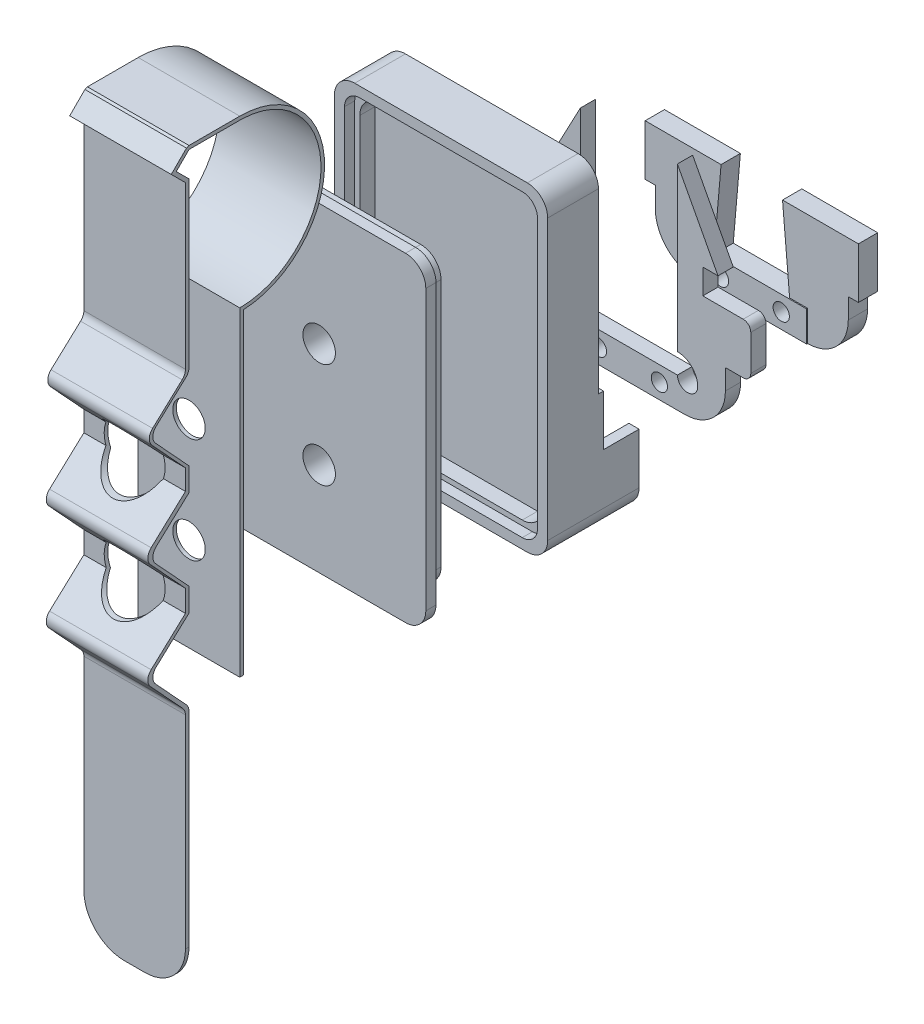
SolidWorks part; units mm, degrees
ref_plane "前视基准面" through (0, 0, 0) normal (0, 0, 1) x (1, 0, 0)
ref_plane "上视基准面" through (0, 0, 0) normal (0, 1, 0) x (1, 0, 0)
ref_plane "右视基准面" through (0, 0, 0) normal (1, 0, 0) x (0, 0, -1)
sketch "草图2" plane through (0, 0, 0) normal (0, 0, 1) x (1, 0, 0)
  line L1 (-21, 31.5) -> (21, 31.5)
  line L2 (-21, 31.5) -> (-21, -31.5)
  line L3 (-21, -31.5) -> (21, -31.5)
  line L4 (21, 31.5) -> (21, -31.5)
  line L5 (-21, 31.5) -> (21, -31.5) construction
  line L6 (-21, -31.5) -> (21, 31.5) construction
  point P0 (0, 0)
extrude "凸台-拉伸1" add sketch "草图2" along normal blind 10
sketch "草图3" plane through (0, 0, 0) normal (0, 0, -1) x (-1, 0, 0)
  line L0 (21, 31.5) -> (21, -31.5) construction
  line L1 (-21, -31.5) -> (21, -31.5)
  line L2 (-21, -31.5) -> (-21, -7.5)
  line L3 (-21, -7.5) -> (21, -7.5)
  line L4 (21, -31.5) -> (21, -7.5)
extrude "凸台-拉伸2" add sketch "草图3" along normal blind 8
sketch "草图4" plane through (0, -7.5, 0) normal (0, 1, 0) x (1, 0, 0)
  line L0 (0, 0) -> (0, 3)
  line L1 (0, 3) -> (5.5, 3)
  line L2 (0, 3) -> (-5.5, 3)
  line L3 (5.5, 3) -> (3.5, 0)
  line L4 (21, 0) -> (-21, 0) construction
  line L5 (-5.5, 3) -> (-3.5, 0)
  line L6 (0, 0) -> (3.5, 0)
  line L7 (0, 0) -> (-3.5, 0)
  line M4 (-21, 0) -> (21, 0)
  dimension "D1" = 3
extrude "凸台-拉伸3" add sketch "草图4" along normal blind 32 contours L2 L5 L0 M4 | L3 L1 L0 M4 region at (-2.287, -7.5, -1.6111) region at (2.287, -7.5, -1.6111)
sketch "草图5" plane through (0, -7.5, 0) normal (0, 1, 0) x (1, 0, 0)
  line L0 (0, 3) -> (0, 5.5)
  line L1 (5.5, 3) -> (-5.5, 3) construction
  line L3 (-5.05, 3) -> (5.05, 3)
  line L4 (-5.05, 3) -> (-5.05, 5.5)
  line L5 (-5.05, 5.5) -> (5.05, 5.5)
  line L6 (5.05, 3) -> (5.05, 5.5)
  line L7 (-5.05, 3) -> (5.05, 5.5) construction
  line L8 (-5.05, 5.5) -> (5.05, 3) construction
  circle A0 centre (1.27, 4.25) radius 0.74
  circle A1 centre (3.81, 4.25) radius 0.74
  circle A2 centre (-1.27, 4.25) radius 0.74
  circle A3 centre (-3.81, 4.25) radius 0.74
  point P5 (0, 4.25)
  dimension "D3" = 1.27
  dimension "D4" = 1.48
  dimension "D1" = 2.5
  dimension "D2" = 10.1
  dimension "D5" = 2
  dimension "D6" = 3
extrude "切除-拉伸1" cut sketch "草图5" against normal through all contours A3 | A2 | A0 | A1 region at (1.27, -7.5, -4.25) region at (3.81, -7.5, -4.25) region at (-1.27, -7.5, -4.25) region at (-3.81, -7.5, -4.25)
fillet "圆角1" radius 3 2 edges at (-4.5, 24.5, -1.5) (4.5, 24.5, -1.5)
sketch "草图6" plane through (0, 0, -8) normal (0, 0, -1) x (-1, 0, 0)
  line L0 (-21, -7.5) -> (-17.55, -7.5)
  line L1 (-3.5, -7.5) -> (-21, -7.5) construction
  line L2 (21, -7.5) -> (17.55, -7.5)
  line L3 (21, -7.5) -> (3.5, -7.5) construction
  line L4 (-17.55, -7.5) -> (-14.55, -7.5)
  line L5 (17.55, -7.5) -> (14.55, -7.5)
  line L6 (21, -7.5) -> (-21, -7.5) construction
  line L7 (-14.55, -7.5) -> (-9.55, -7.5)
  line L8 (14.55, -7.5) -> (9.55, -7.5)
  line L9 (-9.55, -7.5) -> (-7.55, -7.5)
  line L10 (9.55, -7.5) -> (7.55, -7.5)
  line L11 (-21, -31.5) -> (21, -31.5) construction
  line L12 (-21, -7.5) -> (-9.55, -7.5)
  line L13 (-21, -7.5) -> (-21, -17.5)
  line L15 (-9.55, -7.5) -> (-9.55, -19.5)
  line L16 (-21, -17.5) -> (-19, -17.5)
  line L17 (-21, -17.5) -> (-21, -31.5)
  line L19 (-19, -17.5) -> (-19, -21.5)
  line L20 (-21, -17.5) -> (-21, -7.5)
  line L22 (-9.55, -31.5) -> (-9.55, -29.5)
  line L23 (-9.55, -29.5) -> (-11, -29.5)
  line L25 (-9.55, -29.5) -> (0, -29.5)
  line L27 (-9.55, -23.5) -> (0, -23.5)
  line L29 (9.55, -29.5) -> (11, -29.5)
  line L30 (0, -23.5) -> (9.55, -23.5)
  line L32 (0, -29.5) -> (9.55, -29.5)
  line L34 (19, -21.5) -> (19, -17.5)
  line L35 (21, -31.5) -> (21, -7.5) construction
  line L36 (19, -17.5) -> (21, -17.5)
  line L37 (9.55, -19.5) -> (9.55, -7.5)
  line L38 (9.55, -29.5) -> (9.55, -31.5)
  line L39 (21, -7.5) -> (21, -17.5)
  line L40 (-21, -7.5) -> (-21, -17.5)
  arc A0 (-11, -29.5) -> (-19, -21.5) centre (-11, -21.5) cw
  arc A1 (-9.55, -19.5) -> (-13.55, -23.5) centre (-9.55, -23.5) ccw
  arc A2 (-13.55, -23.5) -> (-9.55, -23.5) centre (-11.55, -23.5) ccw
  arc A3 (11, -29.5) -> (19, -21.5) centre (11, -21.5) ccw
  arc A4 (9.55, -23.5) -> (13.55, -23.5) centre (11.55, -23.5) ccw
  arc A5 (13.55, -23.5) -> (9.55, -19.5) centre (9.55, -23.5) ccw
  line M7 (-21, -7.5) -> (-21, -31.5)
  line M9 (21, -31.5) -> (21, -7.5)
  line M10 (21, -7.5) -> (-21, -7.5)
  dimension "D7" = 8
  dimension "D8" = 2
  dimension "D9" = 2
  dimension "D10" = 2
  dimension "D11" = 4
  dimension "D12" = 4
  dimension "D13" = 10
  dimension "D1" = 3.45
  dimension "D2" = 3
  dimension "D3" = 5
  dimension "D4" = 2
  dimension "D5" = 2
  dimension "D6" = 2
  dimension "D14" = 10
extrude "切除-拉伸2" cut sketch "草图6" against normal blind 7 contours A5 A4 L30 L27 A2 A1 L15 L16 L19 A0 L23 L25 L32 L29 A3 L34 L36 L37 M10 M7 M9 region at (19.275, -7.9741, -8)
sketch "草图7" plane through (0, 0, -8) normal (0, 0, -1) x (-1, 0, 0)
  line L0 (-9.55, -7.5) -> (-7.55, -7.5)
  line L1 (9.55, -7.5) -> (-9.55, -7.5) construction
  line L2 (9.55, -7.5) -> (7.55, -7.5)
  line L4 (-7.55, -7.5) -> (-13.55, -7.5)
  line L5 (-7.55, -7.5) -> (-7.55, -25.5)
  line L6 (-7.55, -25.5) -> (-13.55, -25.5)
  line L7 (-13.55, -7.5) -> (-13.55, -25.5)
  line L8 (7.55, -7.5) -> (13.55, -7.5)
  line L9 (7.55, -7.5) -> (7.55, -25.5)
  line L10 (7.55, -25.5) -> (13.55, -25.5)
  line L11 (13.55, -7.5) -> (13.55, -25.5)
  line M3 (9.55, -19.5) -> (9.55, -7.5)
  line M4 (9.55, -7.5) -> (-9.55, -7.5)
  line M5 (-9.55, -7.5) -> (-9.55, -19.5)
  arc M6 (-9.55, -19.5) -> (-13.55, -23.5) centre (-9.55, -23.5) ccw
  arc M7 (-13.55, -23.5) -> (-9.55, -23.5) centre (-11.55, -23.5) ccw
  line M8 (-9.55, -23.5) -> (9.55, -23.5)
  arc M9 (9.55, -23.5) -> (13.55, -23.5) centre (11.55, -23.5) ccw
  arc M10 (13.55, -23.5) -> (9.55, -19.5) centre (9.55, -23.5) ccw
  dimension "D1" = 2
extrude "切除-拉伸3" cut sketch "草图7" against normal blind 7 contours L5 M4 M5 M6 M7 M8 | L9 M4 M8 M9 M10 M3 region at (8.55, -7.6897, -8) region at (-8.55, -7.6897, -8)
sketch "草图8" plane through (0, 0, -1) normal (0, 0, -1) x (-1, 0, 0)
  line L0 (0, -26.5) -> (6, -26.5)
  line L1 (11, -29.5) -> (-11, -29.5) construction
  line L2 (0, -29.5) -> (0, -23.5)
  line L3 (-7.55, -23.5) -> (7.55, -23.5) construction
  line L4 (0, -26.5) -> (-6, -26.5)
  circle A0 centre (-6, -26.5) radius 1.6
  circle A1 centre (6, -26.5) radius 1.6
  dimension "D1" = 6
extrude "切除-拉伸4" cut sketch "草图8" against normal blind 5 contours A1 | A0 region at (-6, -24.9453, -1)
fillet "圆角6" radius 4 4 edges at (21, -31.5, 1) (-21, -31.5, 1) (-21, 31.5, 5) (21, 31.5, 5)
sketch "草图10" plane through (0, 0, 0) normal (0, 0, 1) x (1, 0, 0)
  line L0 (-21, -7.5) -> (-17.55, -7.5)
  line L1 (-21, -7.5) -> (-24, -7.5)
  line L2 (21, -7.5) -> (17.55, -7.5)
  line L3 (-24, -7.5) -> (-24, -17.5)
  line L4 (-17.55, -7.5) -> (-14.55, -7.5)
  line L5 (17.55, -7.5) -> (14.55, -7.5)
  line L6 (-24, -17.5) -> (-21, -17.5)
  line L7 (-14.55, -7.5) -> (-9.55, -7.5)
  line L8 (14.55, -7.5) -> (9.55, -7.5)
  line L9 (-9.55, -7.5) -> (-7.55, -7.5)
  line L10 (9.55, -7.5) -> (7.55, -7.5)
  line L11 (21, -7.5) -> (24, -7.5)
  line L12 (-21, -7.5) -> (-9.55, -7.5)
  line L13 (-21, -7.5) -> (-21, -17.5)
  line L15 (-9.55, -7.5) -> (-9.55, -19.5)
  line L16 (-21, -17.5) -> (-19, -17.5)
  line L17 (-21, -17.5) -> (-21, -31.5)
  line L19 (-19, -17.5) -> (-19, -21.5)
  line L20 (-21, -17.5) -> (-21, -7.5)
  line L22 (-9.55, -31.5) -> (-9.55, -29.5)
  line L23 (-9.55, -29.5) -> (-11, -29.5)
  line L25 (-9.55, -29.5) -> (0, -29.5)
  line L27 (-9.55, -23.5) -> (0, -23.5)
  line L29 (9.55, -29.5) -> (11, -29.5)
  line L30 (0, -23.5) -> (9.55, -23.5)
  line L32 (0, -29.5) -> (9.55, -29.5)
  line L34 (19, -21.5) -> (19, -17.5)
  line L35 (24, -7.5) -> (24, -17.5)
  line L36 (19, -17.5) -> (21, -17.5)
  line L37 (9.55, -19.5) -> (9.55, -7.5)
  line L38 (9.55, -29.5) -> (9.55, -31.5)
  line L39 (21, -7.5) -> (21, -17.5)
  line L40 (-21, -7.5) -> (-21, -17.5)
  line L41 (9.55, -7.5) -> (9.55, 12.5)
  line L42 (9.55, 12.5) -> (17.55, -2.575)
  line L43 (17.55, -2.575) -> (14.55, -2.575)
  line L44 (14.55, -2.575) -> (14.55, -7.5)
  line L45 (-9.55, -7.5) -> (-9.55, 12.5)
  line L46 (-9.55, 12.5) -> (-17.55, -2.575)
  line L47 (-17.55, -2.575) -> (-14.55, -2.575)
  line L48 (-14.55, -2.575) -> (-14.55, -7.5)
  line L49 (24, -17.5) -> (21, -17.5)
  arc A0 (-11, -29.5) -> (-19, -21.5) centre (-11, -21.5) cw
  arc A1 (-9.55, -19.5) -> (-13.55, -23.5) centre (-9.55, -23.5) ccw
  arc A2 (-13.55, -23.5) -> (-9.55, -23.5) centre (-11.55, -23.5) ccw
  arc A3 (11, -29.5) -> (19, -21.5) centre (11, -21.5) ccw
  arc A4 (9.55, -23.5) -> (13.55, -23.5) centre (11.55, -23.5) ccw
  arc A5 (13.55, -23.5) -> (9.55, -19.5) centre (9.55, -23.5) ccw
  circle A6 centre (6, -26.5) radius 1.6
  circle A7 centre (-6, -26.5) radius 1.6
  dimension "D7" = 8
  dimension "D9" = 2
  dimension "D10" = 2
  dimension "D11" = 4
  dimension "D12" = 4
  dimension "D13" = 10
  dimension "D1" = 3.45
  dimension "D2" = 3
  dimension "D3" = 5
  dimension "D4" = 2
  dimension "D5" = 2
  dimension "D6" = 12
  dimension "D14" = 10
extrude "弹性件" add sketch "草图10" along normal blind 3 from offset 30 separate body contours A5 A4 L30 L27 A2 A1 L15 L7 L4 L0 L13 L16 L19 A0 L23 L25 L32 L29 A3 L34 L36 L39 L2 L5 L8 L37 A7 A6 | L44 L43 L42 L41 L8 | L47 L48 L7 L45 L46 | L13 L1 L3 L6 | L49 L35 L11 L39 region at (-22.5, -12.5, 0) region at (-19.275, -7.9741, 0) region at (-12.1683, 0.2789, 0) region at (12.1683, 0.2789, 0) region at (22.5, -12.5, 0) offset against normal yes
fillet "圆角2" radius 1.5 4 edges at (24, -17.5, -28.5) (24, -7.5, -28.5) (-24, -17.5, -28.5) (-24, -7.5, -28.5)
sketch "草图11" plane through (0, 0, -1) normal (0, 0, -1) x (-1, 0, 0)
  line L5 (-11, -29.5) -> (11, -29.5)
  line L6 (-11, -29.5) -> (-11, -23.5)
  line L7 (-11, -23.5) -> (11, -23.5)
  line L8 (11, -29.5) -> (11, -23.5)
extrude "凸台-拉伸6" add sketch "草图11" along normal blind 0.2 from offset 50 separate body
sketch "草图12" plane through (0, 0, -51.2) normal (0, 0, -1) x (-1, 0, 0)
  line L1 (11, -23.5) -> (-11, -23.5) construction
  line L2 (-11, -29.5) -> (11, -29.5)
  line L3 (-21, -17.5) -> (-21, -7.5)
  line L4 (-21, -7.5) -> (-7.55, -7.5)
  line L5 (-7.55, -7.5) -> (-7.55, -14.2821)
  line L6 (-7.55, -7.5) -> (-7.55, -23.5) construction
  line L7 (7.55, -7.5) -> (21, -7.5)
  line L8 (21, -7.5) -> (21, -17.5)
  line L9 (21, -17.5) -> (19, -17.5)
  line L10 (19, -17.5) -> (19, -21.5)
  line L11 (-21, -17.5) -> (-19, -17.5)
  line L12 (-19, -17.5) -> (-19, -21.5)
  line L13 (7.55, -7.5) -> (7.55, -23.5)
  line L14 (-7.55, -14.2821) -> (-7.55, -23.5)
  arc A1 (-19, -21.5) -> (-11, -29.5) centre (-11, -21.5) ccw
  circle A2 centre (-6, -26.5) radius 1.6
  circle A4 centre (6, -26.5) radius 1.6465
  arc A5 (11, -29.5) -> (19, -21.5) centre (11, -21.5) ccw
  line M3 (-11, -23.5) -> (-11, -29.5)
  line M4 (-11, -29.5) -> (11, -29.5)
  line M5 (11, -29.5) -> (11, -23.5)
  line M6 (11, -23.5) -> (-11, -23.5)
extrude "凸台-拉伸7" add sketch "草图12" along normal blind 3.8 contours L12 A1 L14 L5 L4 L3 L11 M3 M6 | A4 A2 M6 M3 M4 M5 | A5 L10 L9 L8 L7 L13 M5 M6 region at (0.0246, -26.5, -51.2) region at (13.9623, -16.7644, -51.2) region at (-13.9623, -16.7644, -51.2)
chamfer "倒角2" distance 1 angle 45 2 edges at (-7.6465, -26.5, -55) (4.4, -26.5, -55)
sketch "草图25" plane through (0, 0, -55) normal (0, 0, -1) x (-1, 0, 0)
  circle A0 centre (6, -26.5) radius 1.6465
  circle A1 centre (-6, -26.5) radius 1.6
extrude "切除-拉伸12" cut sketch "草图25" against normal blind 4.2
chamfer "底座缝隙件" distance 1.5 angle 85 2 edges at (7.55, -7.5, -4.5) (-7.55, -7.5, -4.5) first distance on face at (3.81, -7.5, -3.51)
sketch "草图13" plane through (0, 0, -55) normal (0, 0, -1) x (-1, 0, 0)
  line L0 (-6.05, -7.5) -> (-7.4498, -23.5)
  line L1 (-7.4498, -23.5) -> (-7.55, -23.5)
  line L2 (-7.55, -23.5) -> (-7.55, -7.5)
  line L3 (-7.55, -7.5) -> (-6.05, -7.5)
  line L4 (6.05, -7.5) -> (7.55, -7.5)
  line L5 (7.55, -7.5) -> (7.55, -23.5)
  line L6 (7.55, -23.5) -> (7.4498, -23.5)
  line L7 (7.4498, -23.5) -> (6.05, -7.5)
extrude "盖板缝隙件" add sketch "草图13" against normal blind 3.8
sketch "草图14" plane through (0, 0, 10) normal (0, 0, 1) x (1, 0, 0)
  line L0 (21, -27.5) -> (21, 27.5) construction
  line L1 (-14, -28.5) -> (14, -28.5)
  line L2 (-18, -24.5) -> (-18, 24.5)
  line L3 (-14, 28.5) -> (14, 28.5)
  line L4 (18, -24.5) -> (18, 24.5)
  line L5 (-18, -28.5) -> (18, 28.5) construction
  line L6 (-18, 28.5) -> (18, -28.5) construction
  line L7 (17, 31.5) -> (-17, 31.5) construction
  arc A0 (-14, -28.5) -> (-18, -24.5) centre (-14, -24.5) cw
  arc A1 (14, -28.5) -> (18, -24.5) centre (14, -24.5) ccw
  arc A2 (14, 28.5) -> (18, 24.5) centre (14, 24.5) cw
  arc A3 (-18, 24.5) -> (-14, 28.5) centre (-14, 24.5) cw
  point P0 (0, 0)
  dimension "D3" = 4
  dimension "D1" = 3
  dimension "D2" = 3
extrude "切除-拉伸5" cut sketch "草图14" against normal blind 5
sketch "草图15" plane through (0, 0, 10) normal (0, 0, 1) x (1, 0, 0)
  line L0 (14, 28.5) -> (-14, 28.5) construction
  line L1 (-16, -29.5) -> (16, -29.5)
  line L2 (-19, -26.5) -> (-19, 26.5)
  line L3 (-16, 29.5) -> (16, 29.5)
  line L4 (19, -26.5) -> (19, 26.5)
  line L5 (-19, -29.5) -> (19, 29.5) construction
  line L6 (-19, 29.5) -> (19, -29.5) construction
  line L7 (18, -24.5) -> (18, 24.5) construction
  arc A0 (-16, -29.5) -> (-19, -26.5) centre (-16, -26.5) cw
  arc A1 (16, -29.5) -> (19, -26.5) centre (16, -26.5) ccw
  arc A2 (16, 29.5) -> (19, 26.5) centre (16, 26.5) cw
  arc A3 (-19, 26.5) -> (-16, 29.5) centre (-16, 26.5) cw
  point P0 (0, 0)
  dimension "D3" = 3
  dimension "D1" = 1
  dimension "D2" = 1
extrude "切除-拉伸6" cut sketch "草图15" against normal blind 2
sketch "草图16" plane through (0, 0, 10) normal (0, 0, 1) x (1, 0, 0)
  line L1 (-21, -31.5) -> (21, -31.5)
  line L2 (-21, -31.5) -> (-21, 31.5)
  line L3 (-21, 31.5) -> (21, 31.5)
  line L4 (21, -31.5) -> (21, 31.5)
  line L5 (-21, -31.5) -> (21, 31.5) construction
  line L6 (-21, 31.5) -> (21, -31.5) construction
  point P0 (0, 0)
extrude "凸台-拉伸9" add sketch "草图16" along normal blind 4 from offset 20
sketch "草图19" plane through (0, 0, 30) normal (0, 0, -1) x (-1, 0, 0)
  line L0 (21, 31.5) -> (21, -31.5) construction
  line L1 (-14, -28.5) -> (14, -28.5)
  line L2 (-18, -24.5) -> (-18, 24.5)
  line L3 (-14, 28.5) -> (14, 28.5)
  line L4 (18, -24.5) -> (18, 24.5)
  line L5 (-18, -28.5) -> (18, 28.5) construction
  line L6 (-18, 28.5) -> (18, -28.5) construction
  line L7 (-21, 31.5) -> (21, 31.5) construction
  arc A0 (14, -28.5) -> (18, -24.5) centre (14, -24.5) ccw
  arc A1 (-14, -28.5) -> (-18, -24.5) centre (-14, -24.5) cw
  arc A2 (14, 28.5) -> (18, 24.5) centre (14, 24.5) cw
  arc A3 (-18, 24.5) -> (-14, 28.5) centre (-14, 24.5) cw
  point P0 (0, 0)
  dimension "D3" = 4
  dimension "D1" = 3
  dimension "D2" = 3
extrude "凸台-拉伸10" add sketch "草图19" along normal blind 2
sketch "草图20" plane through (0, 0, 30) normal (0, 0, -1) x (-1, 0, 0)
  line L0 (21, 31.5) -> (21, -31.5) construction
  line L1 (-15, -29.5) -> (15, -29.5)
  line L2 (-19, -25.5) -> (-19, 25.5)
  line L3 (-15, 29.5) -> (15, 29.5)
  line L4 (19, -25.5) -> (19, 25.5)
  line L5 (-19, -29.5) -> (19, 29.5) construction
  line L6 (-19, 29.5) -> (19, -29.5) construction
  line L7 (-21, 31.5) -> (21, 31.5) construction
  line L9 (21, -31.5) -> (-21, -31.5)
  line L10 (21, -31.5) -> (21, 31.5)
  line L11 (21, 31.5) -> (-21, 31.5)
  line L12 (-21, -31.5) -> (-21, 31.5)
  line L13 (21, -31.5) -> (-21, 31.5) construction
  line L14 (21, 31.5) -> (-21, -31.5) construction
  arc A0 (-15, -29.5) -> (-19, -25.5) centre (-15, -25.5) cw
  arc A1 (15, -29.5) -> (19, -25.5) centre (15, -25.5) ccw
  arc A2 (-19, 25.5) -> (-15, 29.5) centre (-15, 25.5) cw
  arc A3 (15, 29.5) -> (19, 25.5) centre (15, 25.5) cw
  point P0 (0, 0)
  point P22 (0, 0)
  dimension "D3" = 4
  dimension "D1" = 2
  dimension "D2" = 2
extrude "切除-拉伸7" cut sketch "草图20" against normal blind 2
sketch "草图21" plane through (0, 0, 0) normal (1, 0, 0) x (0, 0, -1)
  line L0 (-59.6372, -31.5) -> (-59.6372, 31.5)
  line L1 (-59.6372, 63.5) -> (-69.6372, 63.5)
  line L2 (-58.9372, 63.4847) -> (-59.6372, 63.5)
  line L3 (-58.9372, -31.5) -> (-58.9372, 31.5) construction
  line L4 (-69.6372, 25.5) -> (-77.5793, 18.179)
  line L5 (-77.5793, 18.179) -> (-69.6372, 9.5631)
  line L6 (-69.6372, 9.5631) -> (-69.6372, 4.9685)
  line L7 (-69.6372, -10.9685) -> (-69.6372, -15.5631)
  line L8 (-69.6372, 4.9685) -> (-77.5793, -2.3525)
  line L9 (-77.5793, -2.3525) -> (-69.6372, -10.9685)
  line L10 (-69.6372, -15.5631) -> (-77.5793, -22.884)
  line L11 (-69.6372, 63.5) -> (-72.1372, 61)
  line L12 (-69.6372, 58.5) -> (-69.6372, 25.5)
  line L13 (-72.1372, 61) -> (-69.6372, 58.5)
  line L14 (-77.5793, -22.884) -> (-69.6372, -31.5)
  line L15 (-69.6372, 25.5) -> (-69.6372, -10.9685)
  line L16 (-69.6372, -15.5631) -> (-69.6372, -31.5)
  line L17 (-69.6372, -31.5) -> (-69.6372, -80.5)
  line L18 (-58.9372, -31.5) -> (-58.9372, 30.8147)
  line L19 (-59.6372, 64.2) -> (-69.6372, 64.2)
  line L20 (-58.9372, 63.4847) -> (-58.9372, 63.5)
  line L21 (-58.9372, 31.5) -> (-58.9372, 31.5153)
  line L22 (-70.3372, -10.9685) -> (-70.3372, -15.2563)
  line L23 (-70.3372, -15.2563) -> (-78.5685, -22.8438)
  line L24 (-78.5685, -22.8438) -> (-70.3372, -31.7734)
  line L25 (-70.1322, 63.995) -> (-73.1272, 61)
  line L26 (-73.1272, 61) -> (-70.3372, 58.2101)
  line L27 (-70.3372, 58.2101) -> (-70.3372, 25.5)
  line L29 (-70.3372, -31.7734) -> (-70.3372, -80.5)
  line L30 (-70.1322, 63.995) -> (-69.6372, 64.2)
  line L31 (-73.1272, 61) -> (-70.1322, 58.005) construction
  line L33 (-70.3372, 58.5) -> (-70.3372, 25.5) construction
  line L34 (-78.5685, -22.8438) -> (-70.1519, -31.9744) construction
  line L35 (-70.3372, -31.5) -> (-70.3372, -80.5) construction
  line L36 (-70.1117, -15.0484) -> (-78.5685, -22.8438) construction
  line L37 (-70.3372, -10.9685) -> (-70.3372, -15.5631) construction
  line L38 (-70.3372, -10.9685) -> (-78.5685, -2.0388)
  line L39 (-78.5685, -2.0388) -> (-70.3372, 5.5486)
  line L40 (-70.3372, 5.5486) -> (-70.3372, 9.5631)
  line L41 (-70.3372, 9.5631) -> (-78.2793, 18.179)
  line L42 (-78.2793, 18.179) -> (-70.3372, 25.5)
  line L43 (-59.6372, -31.5) -> (-58.9372, -31.5)
  line L44 (-69.6372, -80.5) -> (-70.3372, -80.5)
  arc A0 (-59.6372, 31.5) -> (-58.9372, 63.4847) centre (-59.6372, 47.5) ccw
  arc A1 (-58.9372, 30.8147) -> (-59.6372, 64.2) centre (-59.6372, 47.5) ccw
  arc A2 (-59.6372, 31.5) -> (-59.6372, 63.5) centre (-59.6372, 47.5) ccw construction
  arc A3 (-59.6372, 30.8) -> (-59.6372, 64.2) centre (-59.6372, 47.5) ccw construction
  dimension "D1" = 16
  dimension "D2" = 10
  dimension "D3" = 38
  dimension "D4" = 0.7
extrude "凸台-拉伸11" add sketch "草图21" along normal blind 10 and the other way blind 10 separate body contours L18 A1 L19 L30 L25 L26 L27 L42 L41 L40 L39 L38 L22 L23 L24 L29 L44 L17 L14 L10 L7 L9 L8 L6 L5 L4 L12 L13 L11 L1 L2 A0 L0 L43 region at (0, 0, 59.4882)
fillet "圆角3" radius 2 3 edges at (0, -22.884, 77.5793) (0, -2.3525, 77.5793) (0, 18.179, 77.5793)
fillet "圆角4" radius 2 7 edges at (0, 25.5, 70.3372) (0, -31.7734, 70.3372) (0, -31.5, 69.6372) (0, 25.5, 69.6372) (0, -22.8438, 78.5685) (0, -2.0388, 78.5685) (0, 18.179, 78.2793)
sketch "草图22" plane through (0, 0, 70.3372) normal (0, 0, 1) x (1, 0, 0)
  line L0 (0, 9.5631) -> (0, 5.5486)
  line L1 (-10, 9.5631) -> (10, 9.5631) construction
  line L2 (-10, 5.5486) -> (10, 5.5486) construction
  line L3 (0, -10.9685) -> (0, -15.2563)
  line L4 (-10, -10.9685) -> (10, -10.9685) construction
  line L5 (-10, -15.2563) -> (10, -15.2563) construction
  circle A0 centre (0, 7.5559) radius 6
  circle A1 centre (0, -13.1124) radius 6
  line M3 (-10, 5.5486) -> (10, 5.5486)
  line M5 (10, 9.5631) -> (-10, 9.5631)
extrude "切除-拉伸8" cut sketch "草图22" against normal blind 8 and the other way blind 12 contours A0 M5 | A0 L0 M5 M3 | A0 L0 M3 M5 | A0 M3 | A1 region at (2.944, 7.5559, 70.3372) region at (0, 11.2168, 70.3372) region at (-2.944, 7.5559, 70.3372) region at (0, 3.8949, 70.3372) region at (-5.8303, -13.1124, 70.3372)
sketch "草图23" plane through (0, 0, 59.6372) normal (0, 0, 1) x (1, 0, 0)
  circle A0 centre (0, 7.5559) radius 3.2
  circle A1 centre (0, -13.1124) radius 3.2
extrude "切除-拉伸10" cut sketch "草图23" against normal blind 0.7
sketch "草图24" plane through (0, 0, 34) normal (0, 0, 1) x (1, 0, 0)
  circle A0 centre (0, 7.5559) radius 3.2
  circle A1 centre (0, -13.1124) radius 3.2
extrude "切除-拉伸11" cut sketch "草图24" against normal blind 6
fillet "圆角5" radius 8 2 edges at (10, -80.5, 69.9872) (-10, -80.5, 69.9872)
fillet "圆角7" radius 4 4 edges at (21, -31.5, 33) (-21, -31.5, 33) (-21, 31.5, 33) (21, 31.5, 33)
